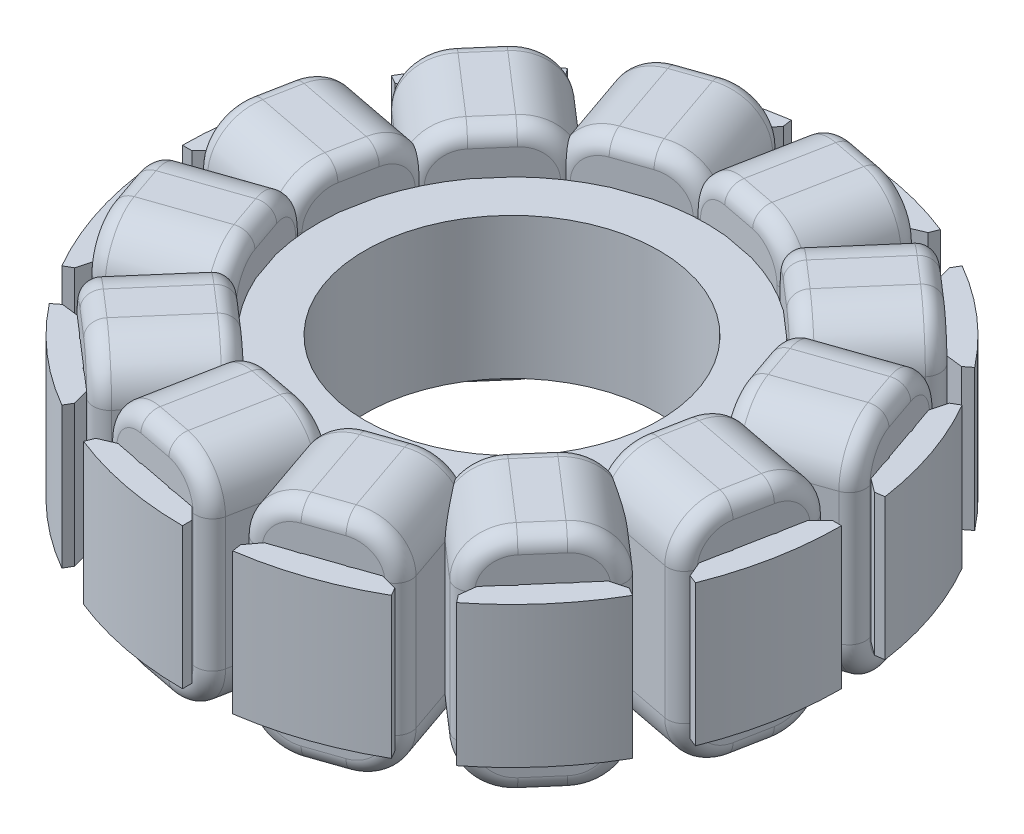
SolidWorks part; units mm, degrees
ref_plane "Спереди" through (0, 0, 0) normal (0, 0, 1) x (1, 0, 0)
ref_plane "Сверху" through (0, 0, 0) normal (0, 1, 0) x (1, 0, 0)
ref_plane "Справа" through (0, 0, 0) normal (1, 0, 0) x (0, 0, -1)
sketch "Эскиз1" plane through (0, 0, 0) normal (0, 1, 0) x (1, 0, 0)
  line L0 (0, 0) -> (0, 20.4324) construction
  line L1 (0, 0) -> (5.2042, 12.9968) construction
  line L2 (0, 0) -> (1.3326, 6.9122) construction
  line L3 (0.8189, 8.2093) -> (1.7204, 12.8857)
  line L6 (2.2917, 7.9253) -> (3.1933, 12.6017)
  line L7 (6.5, 11.2583) -> (7, 12.1244)
  line L8 (10.2193, 8.0353) -> (11.0054, 8.6535)
  line L9 (0, 13) -> (0, 14)
  line L10 (4.8325, 12.0684) -> (5.2042, 12.9968)
  line L11 (5.9474, 5.7176) -> (9.0663, 9.3167)
  line L12 (4.8138, 6.7) -> (7.9328, 10.2991)
  line L13 (11.2583, 6.5) -> (12.1244, 7)
  line L14 (12.8678, 1.8492) -> (13.8576, 1.9914)
  line L15 (8.0094, 1.978) -> (12.51, 3.5354)
  line L16 (7.5189, 3.3955) -> (12.0195, 4.9529)
  line L17 (13, 0) -> (14, 0)
  line L18 (12.0684, -4.8325) -> (12.9968, -5.2042)
  line L19 (7.9253, -2.2917) -> (12.6017, -3.1933)
  line L20 (8.2093, -0.8189) -> (12.8857, -1.7204)
  line L21 (11.2583, -6.5) -> (12.1244, -7)
  line L22 (8.0353, -10.2193) -> (8.6535, -11.0054)
  line L23 (5.7176, -5.9474) -> (9.3167, -9.0663)
  line L24 (6.7, -4.8138) -> (10.2991, -7.9328)
  line L25 (6.5, -11.2583) -> (7, -12.1244)
  line L26 (1.8492, -12.8678) -> (1.9914, -13.8576)
  line L27 (1.978, -8.0094) -> (3.5354, -12.51)
  line L28 (3.3955, -7.5189) -> (4.9529, -12.0195)
  line L29 (0, -13) -> (0, -14)
  line L30 (-4.8325, -12.0684) -> (-5.2042, -12.9968)
  line L31 (-2.2917, -7.9253) -> (-3.1933, -12.6017)
  line L32 (-0.8189, -8.2093) -> (-1.7204, -12.8857)
  line L33 (-6.5, -11.2583) -> (-7, -12.1244)
  line L34 (-10.2193, -8.0353) -> (-11.0054, -8.6535)
  line L35 (-5.9474, -5.7176) -> (-9.0663, -9.3167)
  line L36 (-4.8138, -6.7) -> (-7.9328, -10.2991)
  line L37 (-11.2583, -6.5) -> (-12.1244, -7)
  line L38 (-12.8678, -1.8492) -> (-13.8576, -1.9914)
  line L39 (-8.0094, -1.978) -> (-12.51, -3.5354)
  line L40 (-7.5189, -3.3955) -> (-12.0195, -4.9529)
  line L41 (-13, 0) -> (-14, 0)
  line L42 (-12.0684, 4.8325) -> (-12.9968, 5.2042)
  line L43 (-7.9253, 2.2917) -> (-12.6017, 3.1933)
  line L44 (-8.2093, 0.8189) -> (-12.8857, 1.7204)
  line L45 (-11.2583, 6.5) -> (-12.1244, 7)
  line L46 (-8.0353, 10.2193) -> (-8.6535, 11.0054)
  line L47 (-5.7176, 5.9474) -> (-9.3167, 9.0663)
  line L48 (-6.7, 4.8138) -> (-10.2991, 7.9328)
  line L49 (-6.5, 11.2583) -> (-7, 12.1244)
  line L50 (-1.8492, 12.8678) -> (-1.9914, 13.8576)
  line L51 (-1.978, 8.0094) -> (-3.5354, 12.51)
  line L52 (-3.3955, 7.5189) -> (-4.9529, 12.0195)
  arc A0 (0, 14) -> (5.2042, 12.9968) centre (0, 0) cw
  arc A1 (-3.3955, 7.5189) -> (-5.7176, 5.9474) centre (0, 0) ccw
  circle A2 centre (0, 0) radius 6.25
  arc A3 (0, 13) -> (1.7204, 12.8857) centre (0, 0) cw
  arc A4 (3.1933, 12.6017) -> (4.8325, 12.0684) centre (0, 0) cw
  arc A5 (7, 12.1244) -> (11.0054, 8.6535) centre (0, 0) cw
  arc A6 (6.5, 11.2583) -> (7.9328, 10.2991) centre (0, 0) cw
  arc A7 (9.0663, 9.3167) -> (10.2193, 8.0353) centre (0, 0) cw
  arc A8 (12.1244, 7) -> (13.8576, 1.9914) centre (0, 0) cw
  arc A9 (11.2583, 6.5) -> (12.0195, 4.9529) centre (0, 0) cw
  arc A10 (12.51, 3.5354) -> (12.8678, 1.8492) centre (0, 0) cw
  arc A11 (14, 0) -> (12.9968, -5.2042) centre (0, 0) cw
  arc A12 (13, 0) -> (12.8857, -1.7204) centre (0, 0) cw
  arc A13 (12.6017, -3.1933) -> (12.0684, -4.8325) centre (0, 0) cw
  arc A14 (12.1244, -7) -> (8.6535, -11.0054) centre (0, 0) cw
  arc A15 (11.2583, -6.5) -> (10.2991, -7.9328) centre (0, 0) cw
  arc A16 (9.3167, -9.0663) -> (8.0353, -10.2193) centre (0, 0) cw
  arc A17 (7, -12.1244) -> (1.9914, -13.8576) centre (0, 0) cw
  arc A18 (6.5, -11.2583) -> (4.9529, -12.0195) centre (0, 0) cw
  arc A19 (3.5354, -12.51) -> (1.8492, -12.8678) centre (0, 0) cw
  arc A20 (0, -14) -> (-5.2042, -12.9968) centre (0, 0) cw
  arc A21 (0, -13) -> (-1.7204, -12.8857) centre (0, 0) cw
  arc A22 (-3.1933, -12.6017) -> (-4.8325, -12.0684) centre (0, 0) cw
  arc A23 (-7, -12.1244) -> (-11.0054, -8.6535) centre (0, 0) cw
  arc A24 (-6.5, -11.2583) -> (-7.9328, -10.2991) centre (0, 0) cw
  arc A25 (-9.0663, -9.3167) -> (-10.2193, -8.0353) centre (0, 0) cw
  arc A26 (-12.1244, -7) -> (-13.8576, -1.9914) centre (0, 0) cw
  arc A27 (-11.2583, -6.5) -> (-12.0195, -4.9529) centre (0, 0) cw
  arc A28 (-12.51, -3.5354) -> (-12.8678, -1.8492) centre (0, 0) cw
  arc A29 (-14, 0) -> (-12.9968, 5.2042) centre (0, 0) cw
  arc A30 (-13, 0) -> (-12.8857, 1.7204) centre (0, 0) cw
  arc A31 (-12.6017, 3.1933) -> (-12.0684, 4.8325) centre (0, 0) cw
  arc A32 (-12.1244, 7) -> (-8.6535, 11.0054) centre (0, 0) cw
  arc A33 (-11.2583, 6.5) -> (-10.2991, 7.9328) centre (0, 0) cw
  arc A34 (-9.3167, 9.0663) -> (-8.0353, 10.2193) centre (0, 0) cw
  arc A35 (-7, 12.1244) -> (-1.9914, 13.8576) centre (0, 0) cw
  arc A36 (-6.5, 11.2583) -> (-4.9529, 12.0195) centre (0, 0) cw
  arc A37 (-3.5354, 12.51) -> (-1.8492, 12.8678) centre (0, 0) cw
  arc A38 (0.8189, 8.2093) -> (-1.978, 8.0094) centre (0, 0) ccw
  arc A39 (4.8138, 6.7) -> (2.2917, 7.9253) centre (0, 0) ccw
  arc A40 (7.5189, 3.3955) -> (5.9474, 5.7176) centre (0, 0) ccw
  arc A41 (8.2093, -0.8189) -> (8.0094, 1.978) centre (0, 0) ccw
  arc A42 (6.7, -4.8138) -> (7.9253, -2.2917) centre (0, 0) ccw
  arc A43 (3.3955, -7.5189) -> (5.7176, -5.9474) centre (0, 0) ccw
  arc A44 (-0.8189, -8.2093) -> (1.978, -8.0094) centre (0, 0) ccw
  arc A45 (-4.8138, -6.7) -> (-2.2917, -7.9253) centre (0, 0) ccw
  arc A46 (-7.5189, -3.3955) -> (-5.9474, -5.7176) centre (0, 0) ccw
  arc A47 (-8.2093, 0.8189) -> (-8.0094, -1.978) centre (0, 0) ccw
  arc A48 (-6.7, 4.8138) -> (-7.9253, 2.2917) centre (0, 0) ccw
  point P9 (2.1017, 10.9013)
  point P106 (0, 0)
  dimension "D1" = 14
  dimension "D3" = 16.5
  dimension "D4" = 12.5
  dimension "D7" = 1
  dimension "D2" = 5.3
  dimension "D5" = 21.822
  dimension "D6" = 10.91
  dimension "D8" = 12
  dimension "D9" = 0.75
extrude "Бобышка-Вытянуть1" add sketch "Эскиз1" along normal blind 6
chamfer "Фаска1" distance 0.6 angle 45 24 edges at (6.5, 3, -11.2583) (10.2193, 3, -8.0353) (11.2583, 3, -6.5) (12.8678, 3, -1.8492) (13, 3, 0) (12.0684, 3, 4.8325) (11.2583, 3, 6.5) (8.0353, 3, 10.2193) (6.5, 3, 11.2583) (1.8492, 3, 12.8678) (0, 3, 13) (-4.8325, 3, 12.0684) (-6.5, 3, 11.2583) (-10.2193, 3, 8.0353) (-11.2583, 3, 6.5) (-12.8678, 3, 1.8492) (-12.0684, 3, -4.8325) (-13, 3, 0) (-11.2583, 3, -6.5) (-8.0353, 3, -10.2193) (-6.5, 3, -11.2583) (-1.8492, 3, -12.8678) (4.8325, 3, -12.0684) (0, 3, -13)
sketch "Эскиз2" plane through (0, 0, 0) normal (0, 1, 0) x (1, 0, 0)
  line L0 (-8.0159, 3.3076) -> (-11.5901, 6.4051)
  line L1 (-8.0159, 3.3076) -> (-4.4139, 7.464)
  line L2 (-11.5901, 6.4051) -> (-7.9882, 10.5615)
  line L3 (-4.4139, 7.464) -> (-7.9882, 10.5615)
  line L4 (-8.0159, 3.3076) -> (-7.9882, 10.5615) construction
  line L5 (-11.5901, 6.4051) -> (-4.4139, 7.464) construction
  line L7 (-10.2991, 7.9328) -> (-6.7, 4.8138) construction
  point P1 (-8.002, 6.9346)
  dimension "D1" = 5.5
  dimension "D2" = 2
extrude "Бобышка-Вытянуть2" add sketch "Эскиз2" along normal blind 7.8 and the other way blind 1.8 separate body
fillet "Скругление1" radius 2 4 edges at (-9.803, 7.8, -4.8563) (-6.201, 7.8, -9.0128) (-6.201, -1.8, -9.0128) (-9.803, -1.8, -4.8563)
fillet "Скругление2" radius 0.7 16 edges at (-4.7976, 7.2142, -7.0214) (-4.4139, 3, -7.464) (-4.7976, -1.2142, -7.0214) (-6.2149, -1.8, -5.3858) (-7.6322, -1.2142, -3.7503) (-8.0159, 3, -3.3076) (-7.6322, 7.2142, -3.7503) (-6.2149, 7.8, -5.3858) (-11.2065, -1.2142, -6.8477) (-9.7891, -1.8, -8.4833) (-8.3718, -1.2142, -10.1188) (-7.9882, 3, -10.5615) (-8.3718, 7.2142, -10.1188) (-9.7891, 7.8, -8.4833) (-11.2065, 7.2142, -6.8477) (-11.5901, 3, -6.4051)
sketch "Эскиз3" plane through (0, 0, 0) normal (0, 0, 1) x (1, 0, 0)
  line L0 (0, -5.3232) -> (0, 11.9834) construction
pattern_circular "Круговой массив1" count 12 over 360 about axis through (0, -5.3232, 0) along (0, 1, 0) reverse direction yes of bodies 102
